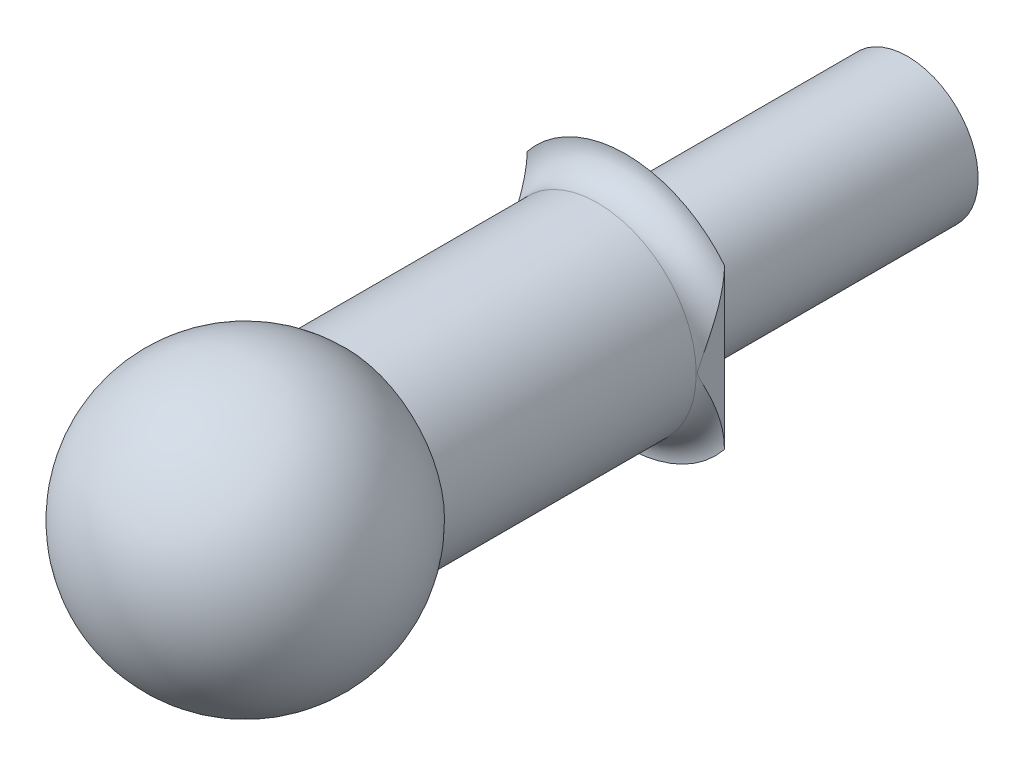
SolidWorks part; units mm, degrees
ref_plane "Front Plane" through (0, 0, 0) normal (0, 0, 1) x (1, 0, 0)
ref_plane "Top Plane" through (0, 0, 0) normal (0, 1, 0) x (1, 0, 0)
ref_plane "Right Plane" through (0, 0, 0) normal (1, 0, 0) x (0, 0, -1)
sketch "Sketch2" plane through (0, 0, 0) normal (0, 0, 1) x (1, 0, 0)
  line L0 (80, 0) -> (-42.1921, 0) construction
  line L2 (-22, -5.5) -> (80, -5.5)
  line L3 (80, -5.5) -> (80, 5.5)
  line L4 (0, 24.5757) -> (0, -40.5685) construction
  line L6 (-22, 5.5) -> (80, 5.5)
  line L7 (-1.5811, -2.25) -> (1.5811, -2.25)
  arc A0 (-22, 5.5) -> (-22, -5.5) centre (-22, 0) ccw
  arc A3 (1.5811, -2.25) -> (-1.5811, -2.25) centre (0, 0) ccw
  point P14 (0, 2.75)
  dimension "D1" = 5.5
  dimension "D5" = 2.75
  dimension "D2" = 80
  dimension "D3" = 22
  dimension "D4" = 5
extrude "Boss-Extrude2" add sketch "Sketch2" along normal mid plane 10
sketch "Sketch3" plane through (80, 0, 0) normal (1, 0, 0) x (0, 0, -1)
  line L0 (33.5, 0) -> (-33.5, 0) construction
  line L1 (-33.5, 0) -> (-33.5, 3.5)
  line L2 (-33.5, 3.5) -> (-21, 3.5)
  line L3 (-20, 4.5) -> (-20, 5)
  line L4 (-19.5, 5.5) -> (19.5, 5.5)
  line L5 (20, 5) -> (20, 4.5)
  line L6 (21, 3.5) -> (33.5, 3.5)
  line L7 (33.5, 3.5) -> (33.5, 0)
  line L8 (33.5, 0) -> (-33.5, 0)
  arc A0 (-21, 3.5) -> (-20, 4.5) centre (-21, 4.5) ccw
  arc A1 (20, 4.5) -> (21, 3.5) centre (21, 4.5) ccw
  arc A2 (-20, 5) -> (-19.5, 5.5) centre (-19.5, 5) cw
  arc A3 (19.5, 5.5) -> (20, 5) centre (19.5, 5) cw
  point P12 (20, 4.75)
  point P13 (0, 5.5)
  point P17 (-20, 5.5)
  point P20 (20, 5.5)
  dimension "D7" = 1
  dimension "D8" = 1
  dimension "D9" = 0.5
  dimension "D10" = 0.5
  dimension "D1" = 40
  dimension "D2" = 13.5
  dimension "D3" = 13.5
  dimension "D4" = 3.5
  dimension "D5" = 5.5
  dimension "D6" = 3.5
revolve "Revolve12" add sketch "Sketch3" angle 360 about L0
sketch "Sketch5" plane through (0, 0, -33.5) normal (0, 0, -1) x (-1, 0, 0)
  line L0 (-80, 5) -> (-80, -5) construction
  line L1 (-80, 5) -> (-80, -5)
  circle A0 centre (-80, 0) radius 5 construction
  arc A1 (-80, 5) -> (-80, -5) centre (-80, 0) ccw
revolve "Revolve16" add sketch "Sketch5" angle 360 about L0
sketch "Sketch6" plane through (0, 0, 33.5) normal (0, 0, 1) x (1, 0, 0)
  line L0 (80, 5) -> (80, -5) construction
  line L1 (80, 5) -> (80, -5)
  circle A0 centre (80, 0) radius 5 construction
  arc A1 (80, 5) -> (80, -5) centre (80, 0) ccw
revolve "Revolve17" add sketch "Sketch6" angle 360 about L0
sketch "Sketch8" plane through (0, 0, 5) normal (0, 0, 1) x (1, 0, 0)
  line L0 (-1.5811, -2.25) -> (1.5811, -2.25)
  circle A0 centre (0, 0) radius 5.5
  arc A1 (1.5811, -2.25) -> (-1.5811, -2.25) centre (0, 0) ccw
  point P6 (0, 2.75)
  dimension "D1" = 2.75
  dimension "D2" = 2.75
  dimension "D3" = 5
extrude "Boss-Extrude5" add sketch "Sketch8" along normal mid plane 20
fillet "Fillet1" radius 2 2 edges at (-5.5, 0, 5) (5.5, 0, 5)
sketch "Sketch9" plane through (0, -2.25, 0) normal (0, 1, 0) x (1, 0, 0)
  line L0 (0, -15) -> (0, -5) construction
  line L1 (-5.5, -15) -> (5.5, -15) construction
  circle A0 centre (0, -10) radius 1.5
  dimension "D1" = 3
extrude "Cut-Extrude1" cut sketch "Sketch9" against normal blind 10
sketch "Sketch10" plane through (0, 5.5, 0) normal (0, 1, 0) x (1, 0, 0)
  line L0 (75.5, -20) -> (84.5, -20) construction
  line L1 (91.6988, -20) -> (-40.0433, -20)
  line L2 (91.6988, -20) -> (91.6988, 40.8738)
  line L3 (91.6988, 40.8738) -> (-40.0433, 40.8738)
  line L4 (-40.0433, -20) -> (-40.0433, 40.8738)
extrude "Cut-Extrude2" cut sketch "Sketch10" against normal blind 30
sketch "Sketch11" plane through (0, 0, 20) normal (0, 0, -1) x (-1, 0, 0)
  line L0 (-78.1002, 1.625) -> (-78.1002, -1.625)
  arc A0 (-78.1002, 1.625) -> (-78.1002, -1.625) centre (-80, 0) ccw
  dimension "D1" = 5
  dimension "D2" = 3.25
extrude "Boss-Extrude6" add sketch "Sketch11" along normal blind 10
sketch "Sketch12" plane through (0, 0, 20) normal (0, 0, -1) x (-1, 0, 0)
  line L0 (-76.4993, 3.57) -> (-76.4993, -3.57)
  line L1 (-83.5007, 3.57) -> (-83.5007, -3.57)
  line L2 (-78.1002, -1.625) -> (-78.1002, 1.625) construction
  circle A0 centre (-80, 0) radius 5
  circle A1 centre (-80, 0) radius 4.5 construction
  point P8 (0, 0)
  point P9 (0, 0)
  dimension "D1" = 10
  dimension "D2" = 7.14
extrude "Cut-Extrude4" cut sketch "Sketch12" against normal blind 9.9 contours L1 L0 | L1 A0 L0 | L0 | L0 A0
